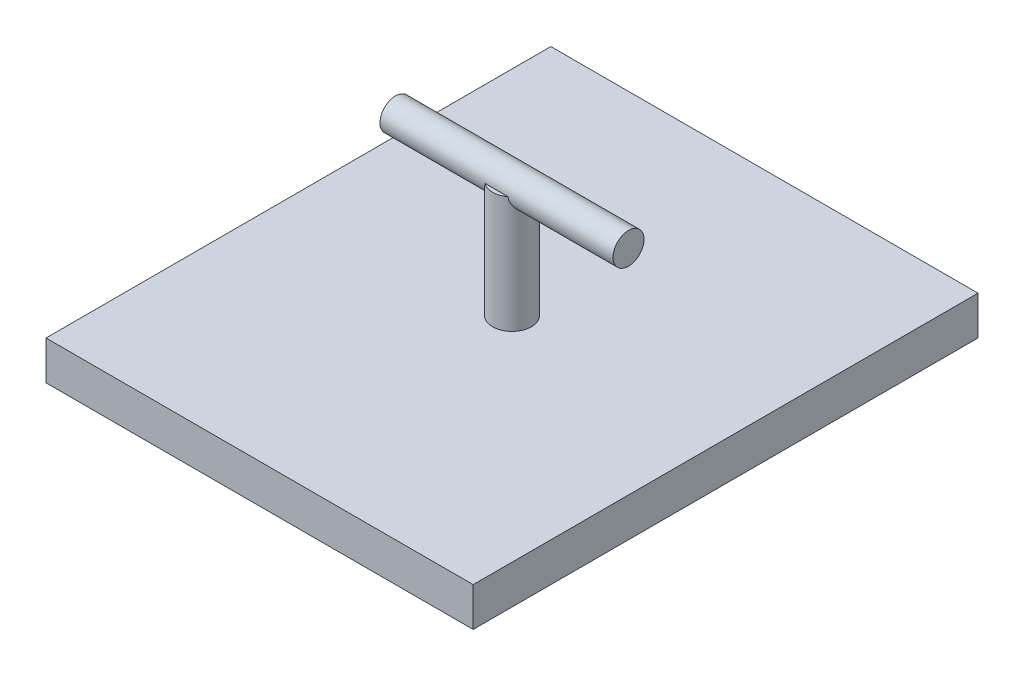
SolidWorks part; units mm, degrees
material "ABS"
ref_plane "前视基准面" through (0, 0, 0) normal (0, 0, 1) x (1, 0, 0)
ref_plane "上视基准面" through (0, 0, 0) normal (0, 1, 0) x (1, 0, 0)
ref_plane "右视基准面" through (0, 0, 0) normal (1, 0, 0) x (0, 0, -1)
sketch "草图1" plane through (0, 0, 0) normal (0, 1, 0) x (1, 0, 0)
  line L0 (-30, 0) -> (30, 0)
  line L1 (-30, 4) -> (30, 4)
  line L2 (-30, 4) -> (-30, -4)
  line L3 (-30, -4) -> (30, -4)
  line L4 (30, 4) -> (30, -4)
  line L5 (-30, 4) -> (30, -4) construction
  line L6 (-30, -4) -> (30, 4) construction
  point P0 (0, 0)
revolve "旋转3" add sketch "草图1" angle 360 about L0 region at (0, 0, -2)
sketch "草图3" plane through (0, 0, 0) normal (0, 1, 0) x (1, 0, 0)
  circle A0 centre (0, 0) radius 5
extrude "凸台-拉伸2" add sketch "草图3" against normal blind 30
sketch "草图5" plane through (0, -30, 0) normal (0, -1, 0) x (1, 0, 0)
  line L1 (-55, 65) -> (55, 65)
  line L2 (-55, 65) -> (-55, -65)
  line L3 (-55, -65) -> (55, -65)
  line L4 (55, 65) -> (55, -65)
  line L5 (-55, 65) -> (55, -65) construction
  line L6 (-55, -65) -> (55, 65) construction
  point P0 (0, 0)
extrude "凸台-拉伸3" add sketch "草图5" along normal blind 10
